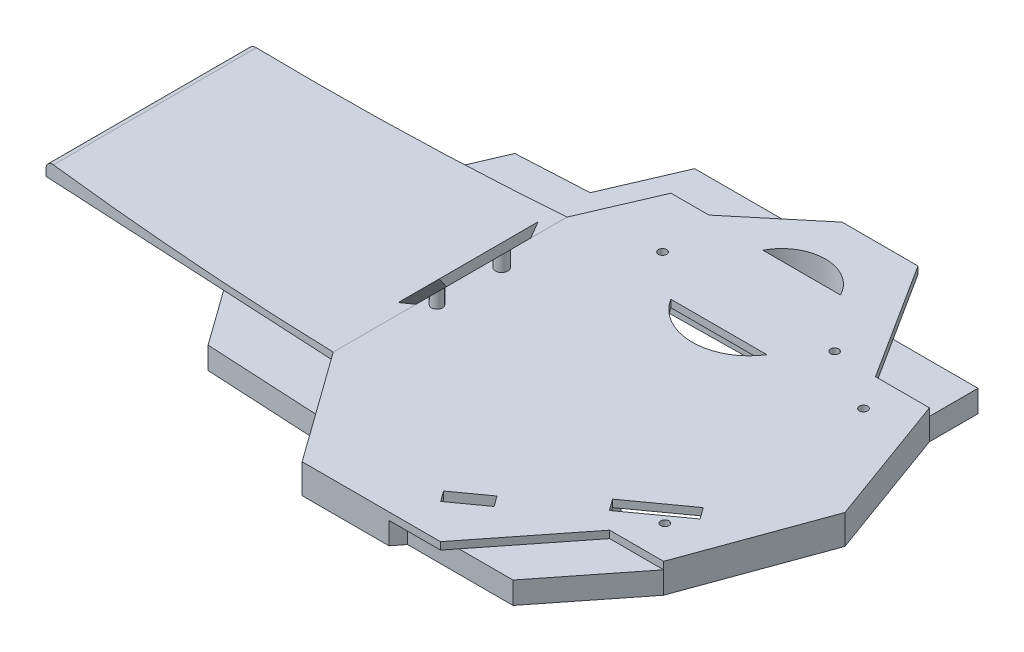
SolidWorks part; units mm, degrees
ref_plane "前视基准面" through (0, 0, 0) normal (0, 0, 1) x (1, 0, 0)
ref_plane "上视基准面" through (0, 0, 0) normal (0, 1, 0) x (1, 0, 0)
ref_plane "右视基准面" through (0, 0, 0) normal (1, 0, 0) x (0, 0, -1)
other "Configuration Table"
sketch "草图2" plane through (0, 0, 0) normal (0, 1, 0) x (1, 0, 0)
  line L0 (0, 0) -> (243.6421, 0) construction
  line L30 (176.8295, 36.1855) -> (82.5273, -31.8251) construction
  line L35 (141.8216, 68.0827) -> (121.1619, 68.0827)
  line L36 (176.8295, 36.1855) -> (190, 0)
  line L37 (104.1466, -61.9173) -> (82.5273, -31.8251)
  line L38 (82.5273, -31.8251) -> (0, -27.5)
  line L39 (0, -27.5) -> (0, 27.5)
  line L40 (0, 27.5) -> (82.5273, 31.8251)
  line L43 (190, 0) -> (176.8295, -36.1855)
  line L45 (82.5273, 31.8251) -> (91.0398, 51.6089)
  line L51 (104.1466, -61.9173) -> (190, 0) construction
  line L53 (141.8216, -61.9173) -> (104.1466, -61.9173)
  line L55 (82.5273, 31.8251) -> (342.4089, 31.8251) construction
  line L57 (176.8295, 36.1855) -> (176.8295, 0) construction
  line L58 (176.8295, 0) -> (176.8295, -36.1855) construction
  line L59 (82.5273, -31.8251) -> (342.4089, -31.8251) construction
  line L62 (91.0398, 51.6089) -> (101.351, 51.6089)
  line L63 (101.351, 51.6089) -> (121.1619, 68.0827)
  line L64 (141.8216, 68.0827) -> (162.1337, 36.1855)
  line L65 (162.1337, 36.1855) -> (176.8295, 36.1855)
  line L66 (176.8295, -36.1855) -> (162.1337, -36.1855)
  line L67 (162.1337, -36.1855) -> (141.8216, -61.9173)
  dimension "D1" = 190
  dimension "D2" = 130
  dimension "D4" = 55
  dimension "D6" = 93
  dimension "D7" = 93
  dimension "D8" = 140
extrude "凸台-拉伸1" add sketch "草图2" along normal blind 2
sketch "草图6" plane through (0, 2, 0) normal (0, 1, 0) x (1, 0, 0)
  line L0 (82.5273, 31.8251) -> (82.5273, -31.8251)
  line L1 (82.5273, -31.8251) -> (0, -27.5)
  line L2 (0, -27.5) -> (0, 27.5)
  line L3 (0, 27.5) -> (82.5273, 31.8251)
extrude "凸台-拉伸2" add sketch "草图6" along normal blind 2
sketch "草图7" plane through (0, 0, 0) normal (0, 0, 1) x (1, 0, 0)
  line L2 (82.5273, 2) -> (82.5273, 30.7408)
  line L3 (82.5273, 30.7408) -> (0, 4)
  spline S0 degree 2 poles (82.5273, 2) (41.2153, 1.0012) (0, 4) knots 0 0 0 1 1 1
extrude "切除-拉伸3" cut sketch "草图7" against normal through all both and the other way through all
fillet "圆角1" radius 2 1 edges at (0, 4, 0)
ref_plane "基准面3" through (0, -12, 0) normal (0, -1, 0) x (-1, 0, 0)
sketch "草图10" plane through (0, 0, 0) normal (0, -1, 0) x (1, 0, 0)
  line L0 (0, 27.5) -> (82.5273, 31.8251)
  line L1 (82.5273, 31.8251) -> (171.8529, 31.8251)
  line L2 (171.8529, 31.8251) -> (171.8529, -31.8251)
  line L3 (171.8529, -31.8251) -> (82.5273, -31.8251)
  line L4 (82.5273, -31.8251) -> (0, -27.5)
  line L5 (0, -27.5) -> (0, 27.5)
sketch "草图12" plane through (0, 2, 0) normal (0, 1, 0) x (1, 0, 0)
  line L0 (176.8295, 36.1855) -> (82.5273, -31.8251)
  line L1 (190, 0) -> (104.1466, -61.9173)
  line L2 (183.4148, 18.0928) -> (93.337, -46.8712) construction
  line L3 (190, 0) -> (176.8295, 36.1855) construction
  line L4 (82.5273, -31.8251) -> (104.1466, -61.9173) construction
sketch "草图13" plane through (0, 0, 0) normal (0, -1, 0) x (1, 0, 0)
  line L0 (53.5015, -30.3039) -> (58.4123, -41.717)
  line L1 (82.5273, -31.8251) -> (0, -27.5) construction
  line L2 (58.4123, -41.717) -> (77.9269, -42.7397)
  line L3 (77.9269, -42.7397) -> (86.4844, -62.6282)
  line L4 (86.4844, -62.6282) -> (136.1647, -62.6282)
  line L5 (176.8295, 36.1855) -> (190, 0)
  line L6 (190, 0) -> (176.8295, -36.1855)
  line L7 (136.1647, -62.6282) -> (144.5841, -49.4069)
  line L8 (144.5841, -49.4069) -> (176.8295, -49.4069)
  line L9 (176.8295, -49.4069) -> (176.8295, -36.1855)
  line L11 (176.8295, 36.1855) -> (158.7432, 59.0976)
  line L12 (158.7432, 59.0976) -> (130.0164, 59.0976)
  line L13 (130.0164, 59.0976) -> (127.7906, 61.9173)
  line L14 (104.1466, 61.9173) -> (141.8216, 61.9173) construction
  line L15 (127.7906, 61.9173) -> (104.1466, 61.9173)
  line L16 (104.1466, 61.9173) -> (93.337, 46.8712)
  line L17 (93.337, 46.8712) -> (61.8459, 45.2208)
  line L18 (61.8459, 45.2208) -> (51.0363, 30.1747)
  line L19 (0, 27.5) -> (82.5273, 31.8251) construction
  line L20 (51.0363, 30.1747) -> (171.8529, 31.8251)
  line L21 (171.8529, 31.8251) -> (171.8529, -31.8251)
  line L22 (171.8529, -31.8251) -> (53.5015, -30.3039)
extrude "凸台-拉伸4" add sketch "草图13" along normal blind 6 contours L18 L20 L21 L22 L0 L2 L3 L4 L7 L8 L9 L6 L5 L11 L12 L13 L15 L16 L17
sketch "草图17" plane through (0, 2, 0) normal (0, 1, 0) x (1, 0, 0)
  line L3 (116.0112, 26.5953) -> (142.1812, 26.5953)
  line L4 (138.1274, 50.6813) -> (116.9896, 50.6813)
  arc A1 (116.0112, 26.5953) -> (142.1812, 26.5953) centre (129.0962, 34.7996) ccw
  arc A2 (116.9896, 50.6813) -> (138.1274, 50.6813) centre (127.5585, 45.2443) cw
sketch "草图18" plane through (0, 2, 0) normal (0, 1, 0) x (1, 0, 0)
  line L4 (169.5639, -18.1259) -> (155.2183, -28.4719)
  line L5 (171.8094, -21.2395) -> (169.5639, -18.1259)
  line L6 (157.4639, -31.5855) -> (171.8094, -21.2395)
  line L7 (155.2183, -28.4719) -> (157.4639, -31.5855)
  line L8 (169.5639, -18.1259) -> (155.2183, -28.4719)
  line L9 (171.8094, -21.2395) -> (169.5639, -18.1259)
  line L10 (157.4639, -31.5855) -> (171.8094, -21.2395)
  line L11 (155.2183, -28.4719) -> (157.4639, -31.5855)
  line L12 (130.3021, -49.5646) -> (132.3616, -52.4203)
  line L13 (132.3616, -52.4203) -> (140.8147, -46.3239)
  line L14 (140.8147, -46.3239) -> (138.7552, -43.4683)
  line L15 (138.7552, -43.4683) -> (130.3021, -49.5646)
  line L16 (130.3021, -49.5646) -> (132.3616, -52.4203)
  line L17 (132.3616, -52.4203) -> (140.8147, -46.3239)
  line L18 (140.8147, -46.3239) -> (138.7552, -43.4683)
  line L19 (138.7552, -43.4683) -> (130.3021, -49.5646)
  dimension "D1" = 0
  dimension "D2" = 0
extrude "切除-拉伸7" cut sketch "草图18" against normal through all
sketch "草图19" plane through (0, 2, 0) normal (0, 1, 0) x (1, 0, 0)
  line L0 (82.5273, -31.8251) -> (176.8295, 36.1855)
  line L1 (176.8295, 36.1855) -> (190, 0)
  line L2 (190, 0) -> (104.1466, -61.9173)
  line L3 (104.1466, -61.9173) -> (82.5273, -31.8251)
ref_plane "基准面4" through (40.2637, -40.2637, 0) normal (-0.7071, 0.7071, 0) x (0, 0, -1)
sketch "草图23" plane through (40.2637, -40.2637, 0) normal (-0.7071, 0.7071, 0) x (0, 0, -1)
  line L0 (-9.292, -59.7699) -> (13.6381, -59.7699)
  line L1 (-31.8251, -59.7699) -> (31.8251, -59.7699) construction
  line L2 (13.6381, -59.7699) -> (13.6381, -71.5206)
  line L3 (13.6381, -71.5206) -> (-9.292, -71.5206)
  line L4 (-9.292, -71.5206) -> (-9.292, -60.8098)
  line L5 (-9.292, -60.8098) -> (-9.292, -59.7699)
extrude "凸台-拉伸5" add sketch "草图23" along normal blind 2 draft 45 separate body draft outward yes
sketch "草图24" plane through (0, 2, 0) normal (0, 1, 0) x (1, 0, 0)
  circle A0 centre (85.4903, 11.0478) radius 1.6973
  circle A1 centre (85.4903, -6.5413) radius 1.5
extrude "凸台-拉伸11" add sketch "草图24" along normal up to surface (2.9629 mm away) separate body contours A0 | A1 region at (85.4903, 2, -11.0478) region at (85.4903, 2, 6.5413) up to face at (86.6818, 6.1545, -2.173)
ref_plane "基准面6" through (0, 4, 0) normal (0, 1, 0) x (1, 0, 0)
sketch "草图25" plane through (0, 4, 0) normal (0, 1, 0) x (1, 0, 0)
  line L1 (67.0613, -53.2409) -> (67.0613, 49.4655) construction
  line L2 (-9.3986, 0) -> (224.1358, 0) construction
  circle A0 centre (67.0613, -25.5664) radius 3
  circle A1 centre (67.0613, 25.5664) radius 3
  circle A2 centre (168.0155, 27.0476) radius 1
  circle A3 centre (168.0155, -27.0476) radius 1
  circle A4 centre (150.7888, 25.9399) radius 3
  circle A5 centre (150.7888, -25.9399) radius 3
  point P11 (168.0155, 27.0476)
  point P14 (168.0155, -27.0476)
extrude "切除-拉伸8" cut sketch "草图17" against normal through all contours L4 A2 | L4 A2 | A1 L3 | A1 L3 region at (129.0962, 2, -23.6319) region at (127.5585, 2, -53.332)
hole_wizard "#4-40 螺纹孔3" positions "草图25" profile "草图26" tap size "#4-40" standard "ANSI Inch" end condition through all
sketch "草图26" plane through (168.0155, 4, 27.0476) normal (1, 0, 0) x (0, 0, 1)
  line L0 (0, 0) -> (0, 10)
  line L1 (0, 10) -> (1.1303, 10)
  line L2 (1.1303, 10) -> (1.1303, 0)
  line L5 (1.1303, 0) -> (0, 0)
  line L11 (0, -6.35) -> (0, 107.95) construction
  dimension "通孔螺纹孔钻头直径" = 2.2606
  dimension "通孔螺纹孔钻头深度" = 10
cosmetic thread "孔螺纹线4" parameters "D2"=2.8448
cosmetic thread "孔螺纹线5" parameters "D2"=2.8448
sketch "草图29" plane through (0, 0, 0) normal (0, -1, 0) x (1, 0, 0)
  circle A0 centre (67.0613, 25.5664) radius 3
  circle A1 centre (67.0613, -25.5664) radius 3
  circle A2 centre (150.7888, 25.9399) radius 3
  circle A3 centre (150.7888, -25.9399) radius 3
extrude "凸台-拉伸14" add sketch "草图29" along normal blind 5 contours A0 | A1 | A2 | A3 region at (67.0613, 0, 25.5664) region at (67.0613, 0, -25.5664) region at (150.7888, 0, 25.9399) region at (150.7888, 0, -25.9399)
sketch "草图33" plane through (0, 2, 0) normal (0, 1, 0) x (1, 0, 0)
  point P0 (150.6025, 36.6082)
  point P3 (103.7494, 36.6082)
hole_wizard "#4-40 螺纹孔4" positions "草图33" profile "草图32" tap size "#4-40" standard "ANSI Inch" end condition through all
sketch "草图32" plane through (150.6025, 2, -36.6082) normal (1, 0, 0) x (0, 0, 1)
  line L0 (0, 0) -> (0, 8)
  line L1 (0, 8) -> (1.1303, 8)
  line L2 (1.1303, 8) -> (1.1303, 0)
  line L5 (1.1303, 0) -> (0, 0)
  line L11 (0, -6.35) -> (0, 107.95) construction
  dimension "通孔螺纹孔钻头直径" = 2.2606
  dimension "通孔螺纹孔钻头深度" = 8
cosmetic thread "孔螺纹线8" parameters "D2"=2.8448
cosmetic thread "孔螺纹线9" parameters "D2"=2.8448
sketch "草图36" plane through (0, 0, 0) normal (0, 1, 0) x (1, 0, 0)
  point P0 (176.7356, -15.6397)
  point P3 (122.1817, -55.0926)
hole_wizard "#4-40 螺纹孔5" positions "草图36" profile "草图35" tap size "#4-40" standard "ANSI Inch" end condition through all
sketch "草图35" plane through (176.7356, 0, 15.6397) normal (1, 0, 0) x (0, 0, 1)
  line L0 (0, 0) -> (0, 6)
  line L1 (0, 6) -> (1.1303, 6)
  line L2 (1.1303, 6) -> (1.1303, 0)
  line L5 (1.1303, 0) -> (0, 0)
  line L11 (0, -6.35) -> (0, 107.95) construction
  dimension "通孔螺纹孔钻头直径" = 2.2606
  dimension "通孔螺纹孔钻头深度" = 6
cosmetic thread "孔螺纹线10" parameters "D2"=2.8448
cosmetic thread "孔螺纹线11" parameters "D2"=2.8448
